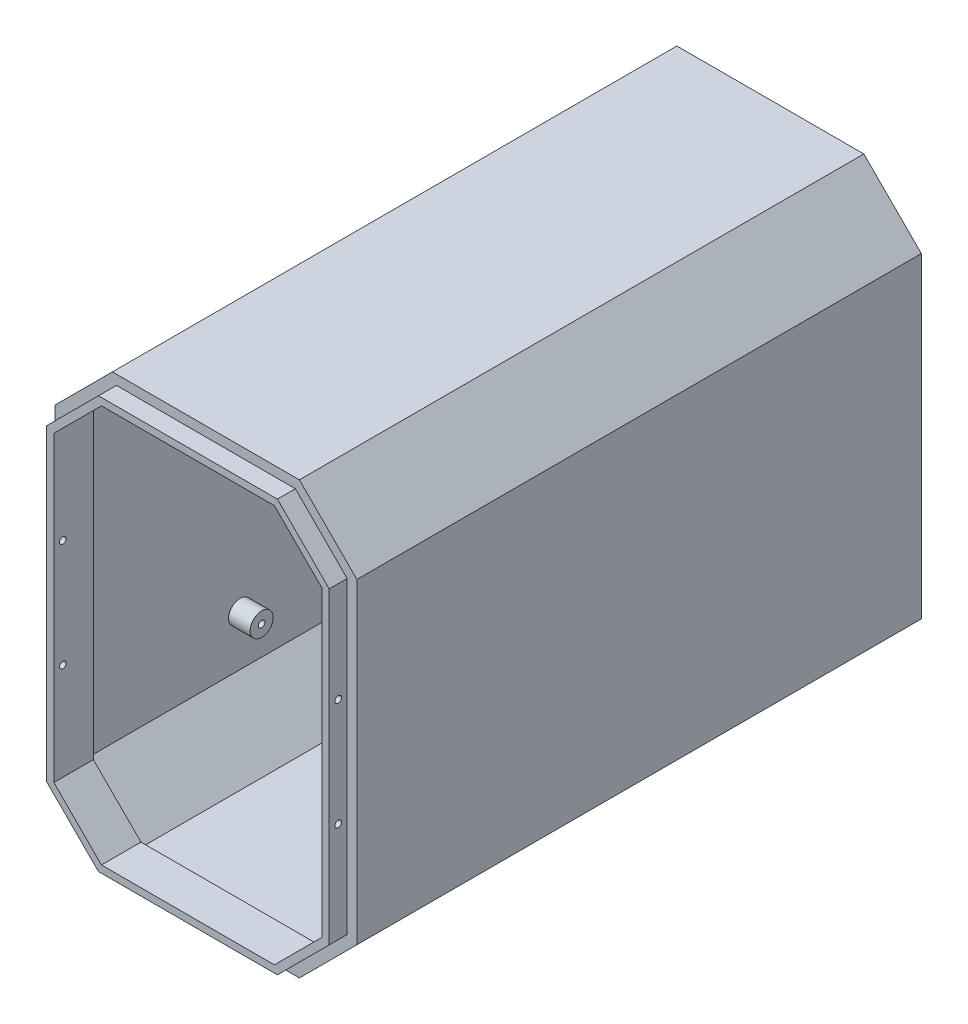
SolidWorks part; units mm, degrees
ref_plane "Front Plane" through (0, 0, 0) normal (0, 0, 1) x (1, 0, 0)
ref_plane "Top Plane" through (0, 0, 0) normal (0, 1, 0) x (1, 0, 0)
ref_plane "Right Plane" through (0, 0, 0) normal (1, 0, 0) x (0, 0, -1)
ref_plane "PZ_p37_000" through (0, 0, 37) normal (0, 0, 1) x (1, 0, 0)
sketch "S_prism1" plane through (0, 0, 37) normal (0, 0, 1) x (1, 0, 0)
  line L0 (42, -44) -> (42, 44)
  line L1 (42, 44) -> (26, 60)
  line L2 (26, 60) -> (-26, 60)
  line L3 (-26, 60) -> (-42, 44)
  line L4 (-42, 44) -> (-42, -44)
  line L5 (-42, -44) -> (-26, -60)
  line L6 (-26, -60) -> (26, -60)
  line L7 (26, -60) -> (42, -44)
extrude "Boss_1" add sketch "S_prism1" along normal blind 157
ref_plane "PZ_p71_425" through (0, 0, 71.425) normal (0, 0, 1) x (1, 0, 0)
sketch "S_pcut2" plane through (0, 0, 71.425) normal (0, 0, 1) x (1, 0, 0)
  line L0 (39.5, -42.9645) -> (39.5, 42.9645)
  line L1 (39.5, 42.9645) -> (24.9645, 57.5)
  line L2 (24.9645, 57.5) -> (-24.9645, 57.5)
  line L3 (-24.9645, 57.5) -> (-39.5, 42.9645)
  line L4 (-39.5, 42.9645) -> (-39.5, -42.9645)
  line L5 (-39.5, -42.9645) -> (-24.9645, -57.5)
  line L6 (-24.9645, -57.5) -> (24.9645, -57.5)
  line L7 (24.9645, -57.5) -> (39.5, -42.9645)
extrude "Cut_2" cut sketch "S_pcut2" along normal blind 122.675
ref_plane "PZ_p36_900" through (0, 0, 36.9) normal (0, 0, 1) x (1, 0, 0)
sketch "S_pcut3" plane through (0, 0, 36.9) normal (0, 0, 1) x (1, 0, 0)
  line L0 (39.5, -42.9645) -> (39.5, 42.9645)
  line L1 (39.5, 42.9645) -> (24.9645, 57.5)
  line L2 (24.9645, 57.5) -> (-24.9645, 57.5)
  line L3 (-24.9645, 57.5) -> (-39.5, 42.9645)
  line L4 (-39.5, 42.9645) -> (-39.5, -42.9645)
  line L5 (-39.5, -42.9645) -> (-24.9645, -57.5)
  line L6 (-24.9645, -57.5) -> (24.9645, -57.5)
  line L7 (24.9645, -57.5) -> (39.5, -42.9645)
extrude "Cut_3" cut sketch "S_pcut3" along normal blind 32.025
ref_plane "PZ_p68_825" through (0, 0, 68.825) normal (0, 0, 1) x (1, 0, 0)
sketch "S_cut4" plane through (0, 0, 68.825) normal (0, 0, 1) x (1, 0, 0)
  line L0 (-34, -14) -> (-26, -14)
  line L1 (-26, -14) -> (-26, 14)
  line L2 (-26, 14) -> (-34, 14)
  line L3 (-34, 14) -> (-34, -14)
  dimension "P1" = 34
  dimension "P2" = 14
  dimension "P3" = 26
  dimension "P4" = 14
  dimension "P5" = 26
  dimension "P6" = 14
  dimension "P7" = 34
  dimension "P8" = 14
extrude "Pocket_4" cut sketch "S_cut4" along normal blind 2.7
ref_plane "PX_m42_100" through (-42.1, 0, 0) normal (1, 0, 0) x (0, 0, -1)
sketch "S_hole5" plane through (-42.1, 0, 0) normal (1, 0, 0) x (0, 0, -1)
  circle A0 centre (-88, 0) radius 6
  dimension "D1_S_hole5" = 12
  dimension "P2" = 88
extrude "Hole_5" cut sketch "S_hole5" along normal blind 2.7
sketch "S_cut6" plane through (0, 0, 68.825) normal (0, 0, 1) x (1, 0, 0)
  line L0 (-9.7, 27.8) -> (9.7, 27.8)
  line L1 (9.7, 27.8) -> (9.7, 34.1)
  line L2 (9.7, 34.1) -> (-9.7, 34.1)
  line L3 (-9.7, 34.1) -> (-9.7, 27.8)
  dimension "P1" = 9.7
  dimension "P2" = 27.8
  dimension "P3" = 9.7
  dimension "P4" = 27.8
  dimension "P5" = 9.7
  dimension "P6" = 34.1
  dimension "P7" = 9.7
  dimension "P8" = 34.1
extrude "Pocket_6" cut sketch "S_cut6" along normal blind 2.7
sketch "S_cut7" plane through (0, 0, 68.825) normal (0, 0, 1) x (1, 0, 0)
  line L0 (-9.7, -34.1) -> (9.7, -34.1)
  line L1 (9.7, -34.1) -> (9.7, -27.8)
  line L2 (9.7, -27.8) -> (-9.7, -27.8)
  line L3 (-9.7, -27.8) -> (-9.7, -34.1)
  dimension "P1" = 9.7
  dimension "P2" = 34.1
  dimension "P3" = 9.7
  dimension "P4" = 34.1
  dimension "P5" = 9.7
  dimension "P6" = 27.8
  dimension "P7" = 9.7
  dimension "P8" = 27.8
extrude "Pocket_7" cut sketch "S_cut7" along normal blind 2.7
sketch "S_hole8" plane through (0, 0, 68.825) normal (0, 0, 1) x (1, 0, 0)
  circle A0 centre (-20, -25) radius 1.7
  dimension "D1_S_hole8" = 3.4
  dimension "P2" = 20
  dimension "P3" = 25
extrude "Hole_8" cut sketch "S_hole8" along normal blind 2.7
sketch "S_hole9" plane through (0, 0, 68.825) normal (0, 0, 1) x (1, 0, 0)
  circle A0 centre (-20, 25) radius 1.7
  dimension "D1_S_hole9" = 3.4
  dimension "P2" = 20
  dimension "P3" = 25
extrude "Hole_9" cut sketch "S_hole9" along normal blind 2.7
sketch "S_hole10" plane through (0, 0, 68.825) normal (0, 0, 1) x (1, 0, 0)
  circle A0 centre (24, -25) radius 1.7
  dimension "D1_S_hole10" = 3.4
  dimension "P2" = 24
  dimension "P3" = 25
extrude "Hole_10" cut sketch "S_hole10" along normal blind 2.7
sketch "S_hole11" plane through (0, 0, 68.825) normal (0, 0, 1) x (1, 0, 0)
  circle A0 centre (24, 25) radius 1.7
  dimension "D1_S_hole11" = 3.4
  dimension "P2" = 24
  dimension "P3" = 25
extrude "Hole_11" cut sketch "S_hole11" along normal blind 2.7
ref_plane "PZ_p188_000" through (0, 0, 188) normal (0, 0, 1) x (1, 0, 0)
sketch "S_prism12" plane through (0, 0, 188) normal (0, 0, 1) x (1, 0, 0)
  line L0 (40, -43.1716) -> (40, 43.1716)
  line L1 (40, 43.1716) -> (25.1716, 58)
  line L2 (25.1716, 58) -> (-25.1716, 58)
  line L3 (-25.1716, 58) -> (-40, 43.1716)
  line L4 (-40, 43.1716) -> (-40, -43.1716)
  line L5 (-40, -43.1716) -> (-25.1716, -58)
  line L6 (-25.1716, -58) -> (25.1716, -58)
  line L7 (25.1716, -58) -> (40, -43.1716)
extrude "Boss_12" add sketch "S_prism12" along normal blind 6
ref_plane "PZ_p193_900" through (0, 0, 193.9) normal (0, 0, 1) x (1, 0, 0)
sketch "S_prism13" plane through (0, 0, 193.9) normal (0, 0, 1) x (1, 0, 0)
  line L0 (39.3, -42.8816) -> (39.3, 42.8816)
  line L1 (39.3, 42.8816) -> (24.8816, 57.3)
  line L2 (24.8816, 57.3) -> (-24.8816, 57.3)
  line L3 (-24.8816, 57.3) -> (-39.3, 42.8816)
  line L4 (-39.3, 42.8816) -> (-39.3, -42.8816)
  line L5 (-39.3, -42.8816) -> (-24.8816, -57.3)
  line L6 (-24.8816, -57.3) -> (24.8816, -57.3)
  line L7 (24.8816, -57.3) -> (39.3, -42.8816)
extrude "Boss_13" add sketch "S_prism13" along normal blind 5.1
ref_plane "PX_m40_000" through (-40, 0, 0) normal (1, 0, 0) x (0, 0, -1)
sketch "S_cyl14" plane through (-40, 0, 0) normal (1, 0, 0) x (0, 0, -1)
  circle A0 centre (-96, -29) radius 3.2
  dimension "D1_S_cyl14" = 6.4
  dimension "P2" = 96
  dimension "P3" = 29
extrude "Boss_14" add sketch "S_cyl14" along normal blind 6.5
sketch "S_cyl15" plane through (-40, 0, 0) normal (1, 0, 0) x (0, 0, -1)
  circle A0 centre (-145, -29) radius 3.2
  dimension "D1_S_cyl15" = 6.4
  dimension "P2" = 145
  dimension "P3" = 29
extrude "Boss_15" add sketch "S_cyl15" along normal blind 6.5
sketch "S_cyl16" plane through (-40, 0, 0) normal (1, 0, 0) x (0, 0, -1)
  circle A0 centre (-96, 29) radius 3.2
  dimension "D1_S_cyl16" = 6.4
  dimension "P2" = 96
  dimension "P3" = 29
extrude "Boss_16" add sketch "S_cyl16" along normal blind 6.5
sketch "S_cyl17" plane through (-40, 0, 0) normal (1, 0, 0) x (0, 0, -1)
  circle A0 centre (-145, 29) radius 3.2
  dimension "D1_S_cyl17" = 6.4
  dimension "P2" = 145
  dimension "P3" = 29
extrude "Boss_17" add sketch "S_cyl17" along normal blind 6.5
ref_plane "PZ_p187_900" through (0, 0, 187.9) normal (0, 0, 1) x (1, 0, 0)
sketch "S_pcut18" plane through (0, 0, 187.9) normal (0, 0, 1) x (1, 0, 0)
  line L0 (37.3, -42.0532) -> (37.3, 42.0532)
  line L1 (37.3, 42.0532) -> (24.0532, 55.3)
  line L2 (24.0532, 55.3) -> (-24.0532, 55.3)
  line L3 (-24.0532, 55.3) -> (-37.3, 42.0532)
  line L4 (-37.3, 42.0532) -> (-37.3, -42.0532)
  line L5 (-37.3, -42.0532) -> (-24.0532, -55.3)
  line L6 (-24.0532, -55.3) -> (24.0532, -55.3)
  line L7 (24.0532, -55.3) -> (37.3, -42.0532)
extrude "Cut_18" cut sketch "S_pcut18" along normal blind 11.2
ref_plane "PX_p37_100" through (37.1, 0, 0) normal (1, 0, 0) x (0, 0, -1)
sketch "S_hole19" plane through (37.1, 0, 0) normal (1, 0, 0) x (0, 0, -1)
  circle A0 centre (-196.5, -15) radius 0.9
  dimension "D1_S_hole19" = 1.8
  dimension "P2" = 196.5
  dimension "P3" = 15
extrude "Hole_19" cut sketch "S_hole19" along normal blind 2.7
sketch "S_hole20" plane through (37.1, 0, 0) normal (1, 0, 0) x (0, 0, -1)
  circle A0 centre (-196.5, 15) radius 0.9
  dimension "D1_S_hole20" = 1.8
  dimension "P2" = 196.5
  dimension "P3" = 15
extrude "Hole_20" cut sketch "S_hole20" along normal blind 2.7
ref_plane "PX_m39_800" through (-39.8, 0, 0) normal (1, 0, 0) x (0, 0, -1)
sketch "S_hole21" plane through (-39.8, 0, 0) normal (1, 0, 0) x (0, 0, -1)
  circle A0 centre (-196.5, -15) radius 0.9
  dimension "D1_S_hole21" = 1.8
  dimension "P2" = 196.5
  dimension "P3" = 15
extrude "Hole_21" cut sketch "S_hole21" along normal blind 2.7
sketch "S_hole22" plane through (-39.8, 0, 0) normal (1, 0, 0) x (0, 0, -1)
  circle A0 centre (-196.5, 15) radius 0.9
  dimension "D1_S_hole22" = 1.8
  dimension "P2" = 196.5
  dimension "P3" = 15
extrude "Hole_22" cut sketch "S_hole22" along normal blind 2.7
ref_plane "PX_m40_600" through (-40.6, 0, 0) normal (1, 0, 0) x (0, 0, -1)
sketch "S_hole23" plane through (-40.6, 0, 0) normal (1, 0, 0) x (0, 0, -1)
  circle A0 centre (-96, -29) radius 0.9
  dimension "D1_S_hole23" = 1.8
  dimension "P2" = 96
  dimension "P3" = 29
extrude "Hole_23" cut sketch "S_hole23" along normal blind 7.2
sketch "S_hole24" plane through (-40.6, 0, 0) normal (1, 0, 0) x (0, 0, -1)
  circle A0 centre (-145, -29) radius 0.9
  dimension "D1_S_hole24" = 1.8
  dimension "P2" = 145
  dimension "P3" = 29
extrude "Hole_24" cut sketch "S_hole24" along normal blind 7.2
sketch "S_hole25" plane through (-40.6, 0, 0) normal (1, 0, 0) x (0, 0, -1)
  circle A0 centre (-96, 29) radius 0.9
  dimension "D1_S_hole25" = 1.8
  dimension "P2" = 96
  dimension "P3" = 29
extrude "Hole_25" cut sketch "S_hole25" along normal blind 7.2
sketch "S_hole26" plane through (-40.6, 0, 0) normal (1, 0, 0) x (0, 0, -1)
  circle A0 centre (-145, 29) radius 0.9
  dimension "D1_S_hole26" = 1.8
  dimension "P2" = 145
  dimension "P3" = 29
extrude "Hole_26" cut sketch "S_hole26" along normal blind 7.2
equation "\"plate_t\" = 3"
equation "\"clearance\" = 0.5"
